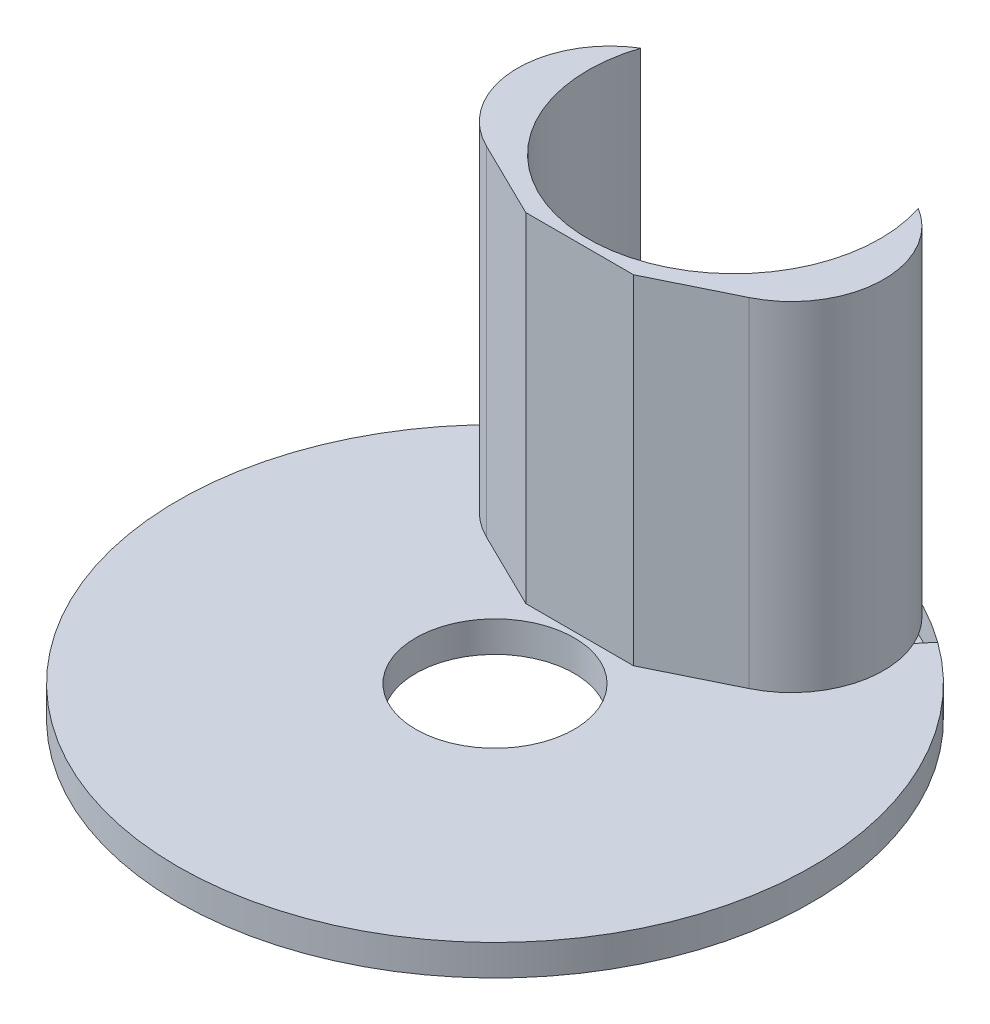
SolidWorks part; units mm, degrees
ref_plane "Front Plane" through (0, 0, 0) normal (0, 0, 1) x (1, 0, 0)
ref_plane "Top Plane" through (0, 0, 0) normal (0, 1, 0) x (1, 0, 0)
ref_plane "Right Plane" through (0, 0, 0) normal (1, 0, 0) x (0, 0, -1)
sketch "Sketch1" plane through (0, 0, 0) normal (0, 1, 0) x (1, 0, 0)
  circle A0 centre (0, 0) radius 20.6
  dimension "D1" = 41.2
extrude "Boss-Extrude1" add sketch "Sketch1" along normal blind 2
sketch "Sketch2" plane through (0, 2, 0) normal (0, 1, 0) x (1, 0, 0)
  circle A0 centre (0, 0) radius 5.15
  dimension "D1" = 10.3
extrude "Cut-Extrude1" cut sketch "Sketch2" against normal blind 3
sketch "Sketch3" plane through (0, 2, 0) normal (0, 1, 0) x (1, 0, 0)
  circle A0 centre (0, 13) radius 6.5
  dimension "D2" = 13
  dimension "D1" = 13
extrude "Cut-Extrude2" cut sketch "Sketch3" against normal blind 2
sketch "Sketch4" plane through (0, 2, 0) normal (0, 1, 0) x (1, 0, 0)
  line L0 (-3.5, 5.5) -> (-16.744, 12)
  line L1 (3.5, 5.5) -> (16.744, 12)
  line L4 (-3.5, 5.5) -> (3.5, 5.5)
  arc A0 (-16.744, 12) -> (-9, 18.53) centre (0, 0) cw
  circle A1 centre (0, 0) radius 20.6 construction
  arc A4 (9, 18.53) -> (16.744, 12) centre (0, 0) cw
  arc A6 (-9, 18.53) -> (9, 18.53) centre (0, 15.5297) ccw
  dimension "D1" = 12
  dimension "D2" = 12
  dimension "D3" = 5.5
  dimension "D4" = 5.5
  dimension "D5" = 3.5
  dimension "D6" = 3.5
  dimension "D7" = 9
  dimension "D8" = 9
extrude "Boss-Extrude4" add sketch "Sketch4" along normal blind 22
fillet "Fillet2" radius 6 2 edges at (16.744, 13, -12) (-16.744, 13, -12)
